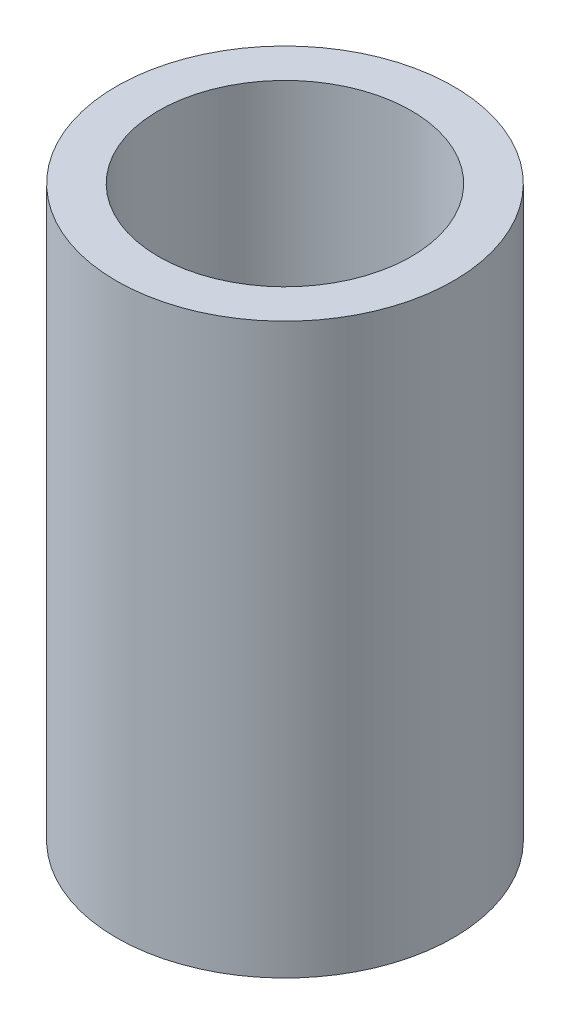
SolidWorks part; units mm, degrees
ref_plane "Front Plane" through (0, 0, 0) normal (0, 0, 1) x (1, 0, 0)
ref_plane "Top Plane" through (0, 0, 0) normal (0, 1, 0) x (1, 0, 0)
ref_plane "Right Plane" through (0, 0, 0) normal (1, 0, 0) x (0, 0, -1)
sketch "Sketch1" plane through (0, 0, 0) normal (0, 1, 0) x (1, 0, 0)
  circle A0 centre (0, 0) radius 6
  circle A1 centre (0, 0) radius 8
  dimension "D1" = 12
  dimension "D2" = 16
extrude "Boss-Extrude1" add sketch "Sketch1" along normal blind 27
